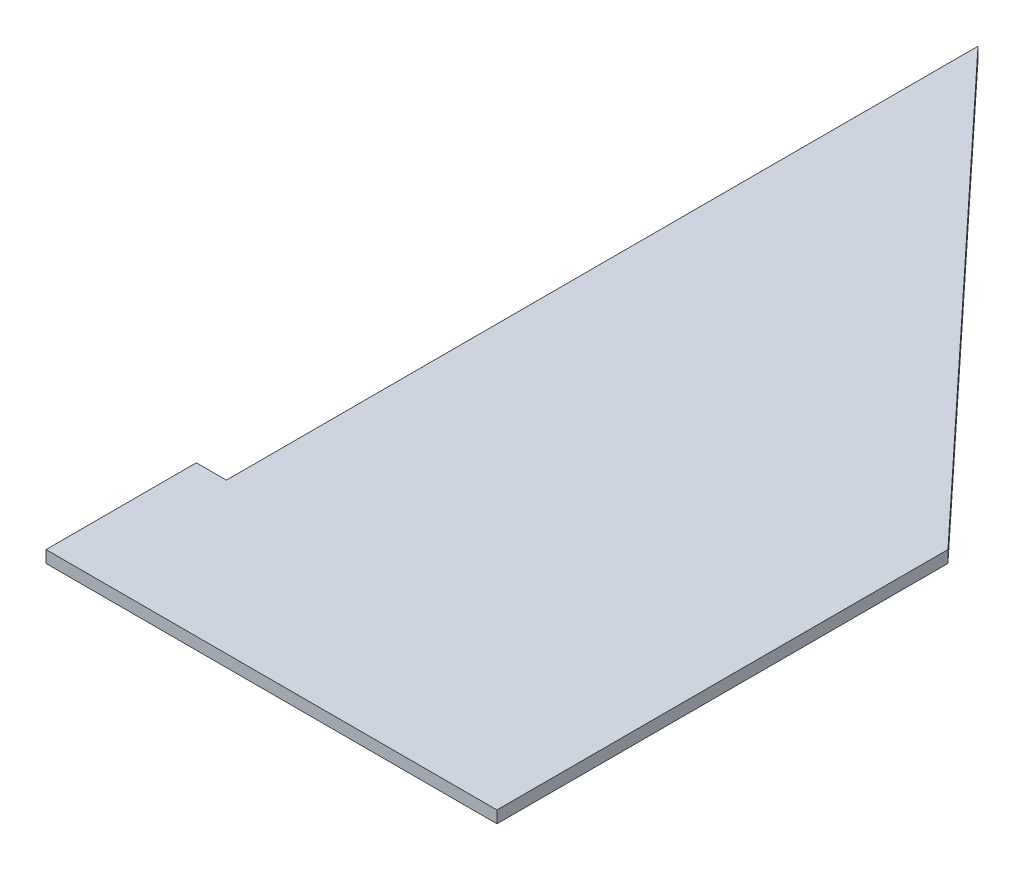
SolidWorks part; units mm, degrees
material "Fibra di Carbonio"
ref_plane "Piano frontale" through (0, 0, 0) normal (0, 0, 1) x (1, 0, 0)
ref_plane "Piano superiore" through (0, 0, 0) normal (0, 1, 0) x (1, 0, 0)
ref_plane "Piano destro" through (0, 0, 0) normal (1, 0, 0) x (0, 0, -1)
sketch "Forma aletta" plane through (0, 0, 0) normal (0, 1, 0) x (1, 0, 0)
  line L0 (0, 0) -> (0, 300) construction
  line L1 (0, 300) -> (0, 50)
  line L2 (0, 0) -> (140, 0)
  line L3 (140, 0) -> (140, 150)
  line L4 (140, 150) -> (0, 300)
  line L5 (0, 0) -> (-10, 0)
  line L6 (-10, 0) -> (-10, 50)
  line L7 (-10, 50) -> (0, 50)
  dimension "D1" = 300
  dimension "D2" = 150
  dimension "D3" = 205.1828
  dimension "D4" = 50
  dimension "D6" = 140
extrude "Estrusione-Estrusione1" add sketch "Forma aletta" along normal blind 2 and the other way blind 2
